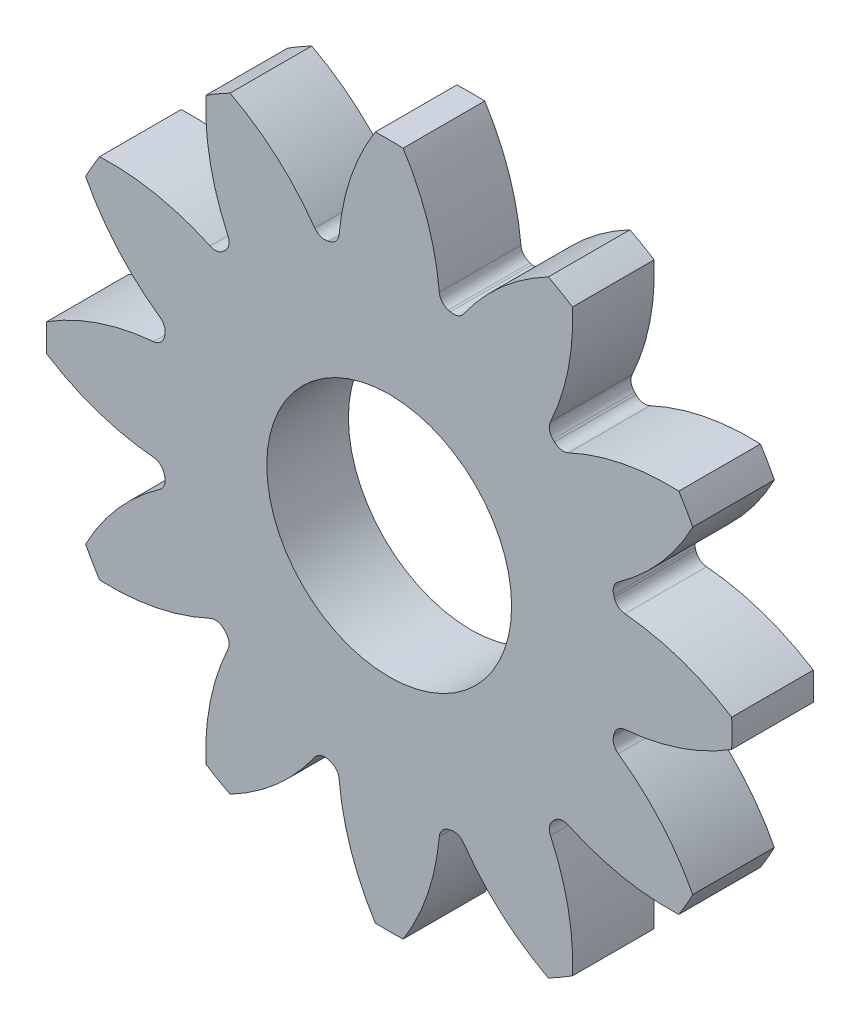
SolidWorks part; units mm, degrees
ref_plane "정면" through (0, 0, 0) normal (0, 0, 1) x (1, 0, 0)
ref_plane "윗면" through (0, 0, 0) normal (0, 1, 0) x (1, 0, 0)
ref_plane "우측면" through (0, 0, 0) normal (1, 0, 0) x (0, 0, -1)
sketch "스케치1" plane through (0, 0, 0) normal (0, 0, 1) x (1, 0, 0)
  line L0 (0, 23.3301) -> (0, -28.0899) construction
  line L1 (-2.355, 17.8453) -> (-2.355, -28.0899) construction
  line L2 (-3.105, 13.9076) -> (-3.105, -28.0899) construction
  line L3 (-0.855, 20.9826) -> (-0.855, -28.0899) construction
  line L4 (-3.105, 23.3301) -> (-3.105, -28.0899) construction
  line L5 (-2.355, 23.3301) -> (-2.355, -28.0899) construction
  line L6 (-0.855, 23.3301) -> (-0.855, -28.0899) construction
  circle A0 centre (0, 0) radius 14.25
  circle A1 centre (0, 0) radius 21
  circle A2 centre (0, 0) radius 18 construction
  arc A3 (-3.105, 13.9076) -> (-0.855, 20.9826) centre (11.4379, 13.1779) cw
  arc A4 (3.105, 13.9076) -> (0.855, 20.9826) centre (-11.4379, 13.1779) ccw
  dimension "D1" = 28.5
  dimension "D2" = 36
  dimension "D3" = 42
  dimension "D4" = 2.355
  dimension "D5" = 0.75
  dimension "D6" = 1.5
extrude "보스-돌출1" add sketch "스케치1" along normal blind 5 contours A0 region at (0, 0, 0)
extrude "보스-돌출2" add sketch "스케치1<3>" along normal blind 5 contours A0 A1 region at (0, 17.0122, 0)
sketch "스케치1<3>" plane through (0, 0, 0) normal (0, 0, 1) x (1, 0, 0) same geometry as "스케치1"
sketch "스케치2" plane through (0, 0, 5) normal (0, 0, 1) x (1, 0, 0)
  circle A0 centre (0, 0) radius 7.5
  dimension "D1" = 15
extrude "컷-돌출1" cut sketch "스케치2" against normal up to next
fillet "필렛1" radius 0.75 2 edges at (3.105, 13.9076, 2.5) (-3.105, 13.9076, 2.5)
pattern_circular "원형 패턴2" count 12 over 360 about axis through (0, 0, -0.001) along (0, 0, 1) of "필렛1", "보스-돌출2" reverse direction yes
